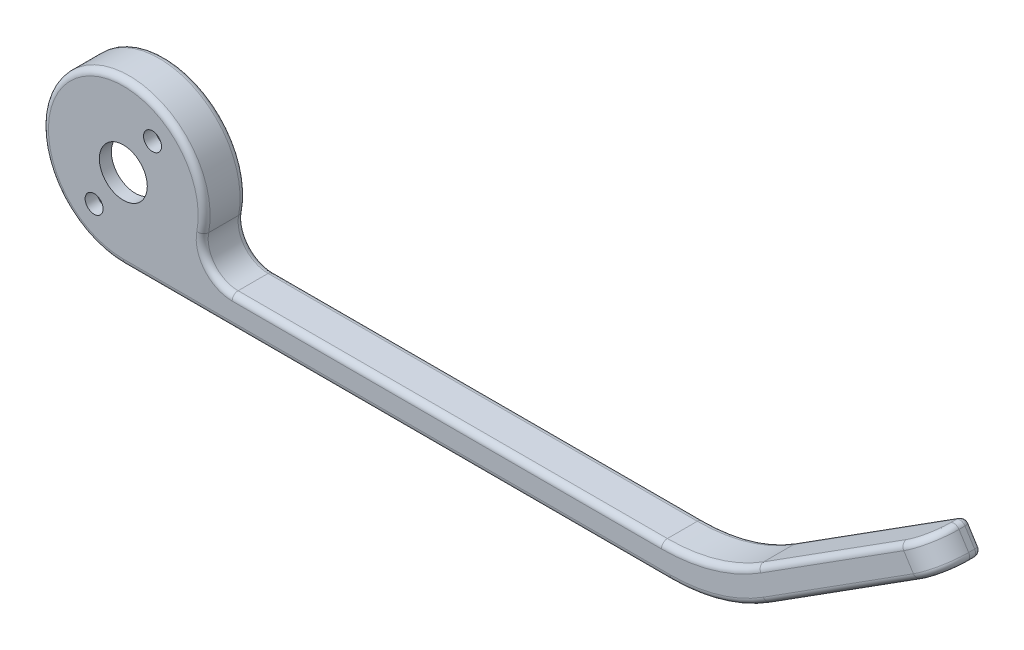
SolidWorks part; units mm, degrees
material "ABS"
ref_plane "Front" through (0, 0, 0) normal (0, 0, 1) x (1, 0, 0)
ref_plane "Top" through (0, 0, 0) normal (0, 1, 0) x (1, 0, 0)
ref_plane "Right" through (0, 0, 0) normal (1, 0, 0) x (0, 0, -1)
sketch "Esquisse1" plane through (0, 0, 0) normal (0, 0, 1) x (1, 0, 0)
  line L2 (10.4881, -8.5) -> (98.5463, -8.5)
  line L3 (0, -13.5) -> (100, -13.5)
  line L4 (98.5463, -8.5) -> (133.9697, 14)
  line L5 (133.9697, 14) -> (136.6505, 9.7794)
  line L6 (136.6505, 9.7794) -> (100, -13.5)
  arc A0 (10.4881, -8.5) -> (0, -13.5) centre (0, 0) ccw
  circle A1 centre (0, 0) radius 4
  dimension "D1" = 13.5
  dimension "D4" = 8
  dimension "D5" = 137
  dimension "D7" = 14
  dimension "D6" = 100
  dimension "D2" = 5
  dimension "D3" = 5
extrude "Boss.-Extru.1" add sketch "Esquisse1" along normal mid plane 7
fillet "Congé1" radius 5 2 edges at (10.4881, -8.5, 0) (135.3101, 11.8897, 3.5)
sketch "Esquisse5" plane through (0, 0, 3.5) normal (0, 0, 1) x (1, 0, 0)
  circle A0 centre (0, 0) radius 12.25
  circle A1 centre (0, 0) radius 4 construction
  dimension "D1" = 24.5
extrude "Enlèv. mat.-Extru.3" cut sketch "Esquisse5" against normal through all from offset 2 offset against normal yes
sketch "Esquisse6" plane through (0, 0, 3.5) normal (0, 0, 1) x (1, 0, 0)
  line L0 (-4.8754, -6.9628) -> (4.8754, 6.9628) construction
  line L2 (0, -50) -> (0, 50) construction
  circle A0 centre (4.8754, 6.9628) radius 1.5
  circle A1 centre (-4.8754, -6.9628) radius 1.5
  circle A2 centre (0, 0) radius 4 construction
  point P4 (0, 0)
  dimension "D1" = 3
  dimension "D2" = 17
  dimension "D3" = 35
extrude "Enlèv. mat.-Extru.4" cut sketch "Esquisse6" against normal through all
fillet "Congé3" radius 30 2 edges at (100, -13.5, 0) (98.5463, -8.5, 0)
fillet "Congé2" radius 1 21 edges at (53.995, -8.5, 3.5) (45.6389, -13.5, 3.5) (53.995, -8.5, -3.5) (45.6389, -13.5, -3.5) (-8.5956, 10.4098, 3.5) (-8.5956, 10.4098, -3.5) (117.829, 3.7479, 3.5) (98.1995, -7.3072, 3.5) (119.8963, -0.8624, 3.5) (99.6532, -12.3072, 3.5) (119.9393, 5.0883, -3.5) (98.1995, -7.3072, -3.5) (122.0065, 0.478, -3.5) (99.6532, -12.3072, -3.5) (136.6505, 9.7794, -2.5) (133.9697, 14, -2.5) (135.3101, 11.8897, -3.5) (14.3104, -6.6836, -3.5) (14.3104, -6.6836, 3.5) (132.7335, 13.2148, 2.0355) (135.4143, 8.9942, 2.0355)
